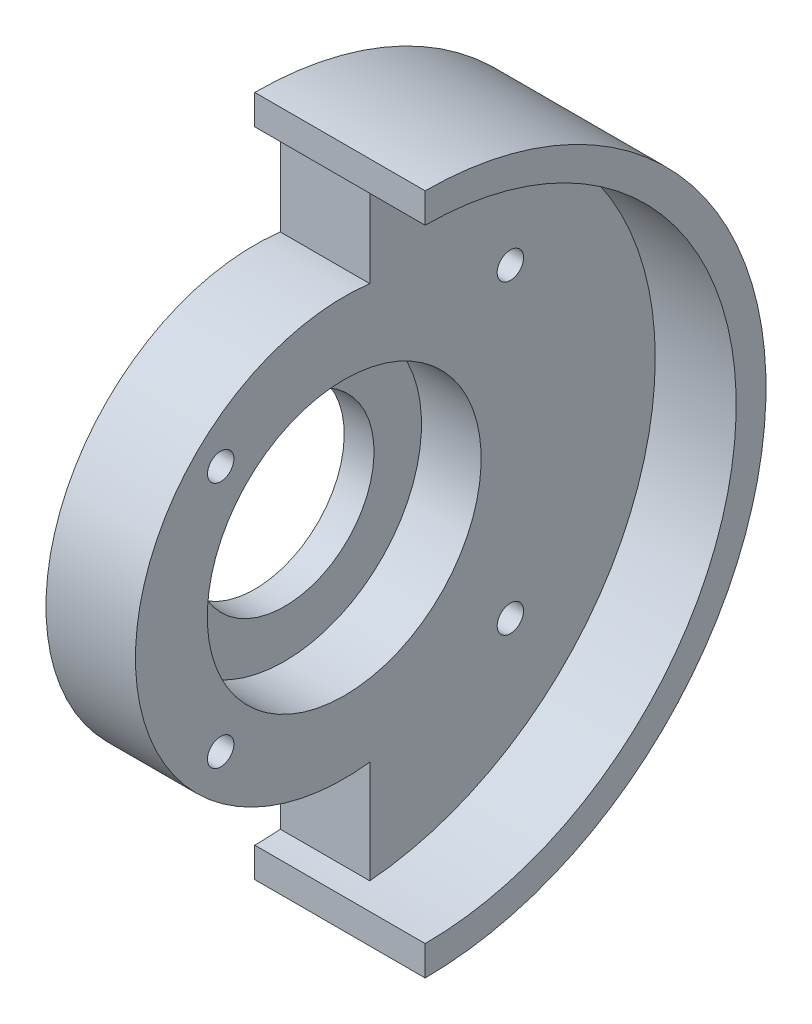
SolidWorks part; units mm, degrees
material "PLA 3D print"
ref_plane "Front Plane" through (0, 0, 0) normal (0, 0, 1) x (1, 0, 0)
ref_plane "Top Plane" through (0, 0, 0) normal (0, 1, 0) x (1, 0, 0)
ref_plane "Right Plane" through (0, 0, 0) normal (1, 0, 0) x (0, 0, -1)
sketch "Sketch1" plane through (0, 0, 0) normal (0, 0, 1) x (1, 0, 0)
  line L0 (20, 40) -> (20, 36.5)
  line L1 (20, 36.5) -> (10.5, 36.5)
  line L2 (10.5, 36.5) -> (10.5, 16.07)
  line L3 (10.5, 16.07) -> (3.5, 16.07)
  line L4 (3.5, 16.07) -> (3.5, 10.5)
  line L5 (3.5, 10.5) -> (0, 10.5)
  line L6 (0, 10.5) -> (0, 40)
  line L7 (0, 40) -> (20, 40)
  line L8 (20, 0) -> (0, 0) construction
  dimension "D1" = 20
  dimension "D2" = 7
  dimension "D3" = 9.5
  dimension "D4" = 10.5
  dimension "D5" = 16.07
  dimension "D6" = 36.5
  dimension "D7" = 40
revolve "Revolve1" add sketch "Sketch1" angle 360 about L8
sketch "Sketch2" plane through (10.5, 0, 0) normal (1, 0, 0) x (0, 0, -1)
  line L0 (3, 24.3156) -> (3, 36.3765)
  line L1 (3, -24.3156) -> (3, -36.3765)
  line L2 (0, 40) -> (0, 36.5)
  line L3 (0, -36.5) -> (0, -40)
  arc A0 (3, 36.3765) -> (0, 36.5) centre (0, 0) ccw
  arc A1 (3, 24.3156) -> (3, -24.3156) centre (0, 0) ccw
  circle A2 centre (-14.4957, 14.4957) radius 1.55
  circle A3 centre (0, 0) radius 36.5 construction
  arc A4 (3, 24.3156) -> (3, -24.3156) centre (0, 0) ccw construction
  circle A5 centre (19.5, -17.9444) radius 1.55
  circle A6 centre (19.5, 17.9444) radius 1.55
  circle A7 centre (19.5, 17.9444) radius 1.55 construction
  circle A9 centre (19.5, -17.9444) radius 1.55 construction
  arc A10 (0, 40) -> (0, -40) centre (0, 0) ccw
  circle A11 centre (0, 0) radius 40 construction
  arc A12 (0, -36.5) -> (3, -36.3765) centre (0, 0) ccw
  circle A13 centre (-14.4957, 14.4957) radius 1.55 construction
  circle A14 centre (-14.4957, -14.4957) radius 1.55
  circle A15 centre (-14.4957, -14.4957) radius 1.55 construction
extrude "Cut-Extrude1" cut sketch "Sketch2" against normal through all both and the other way through all
sketch "Sketch3" plane through (0, 0, 0) normal (-1, 0, 0) x (0, 0, 1)
  circle A0 centre (-19.5, 17.9444) radius 2.95
  circle A1 centre (14.4957, 14.4957) radius 2.95
  circle A2 centre (-19.5, -17.9444) radius 2.95
  circle A3 centre (14.4957, -14.4957) radius 2.95
  dimension "D1" = 5.9
extrude "Cut-Extrude2" cut sketch "Sketch3" against normal blind 4.9
